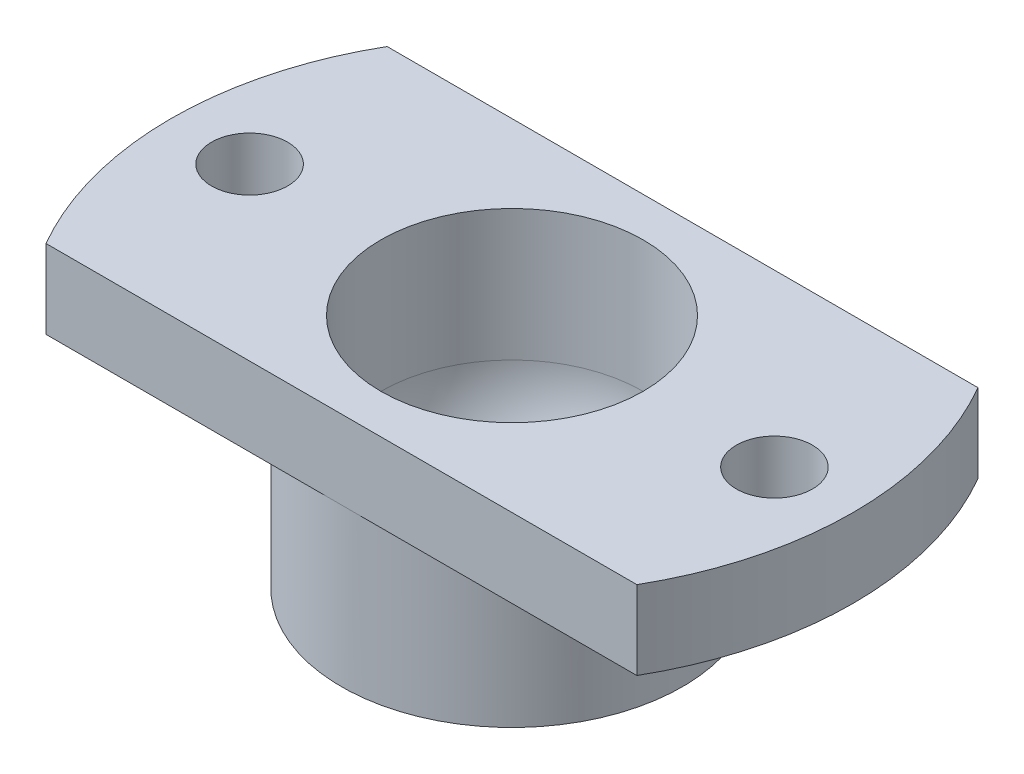
SolidWorks part; units mm, degrees
material "ABS"
ref_plane "Front Plane" through (0, 0, 0) normal (0, 0, 1) x (1, 0, 0)
ref_plane "Top Plane" through (0, 0, 0) normal (0, 1, 0) x (1, 0, 0)
ref_plane "Right Plane" through (0, 0, 0) normal (1, 0, 0) x (0, 0, -1)
sketch "Sketch1" plane through (0, 0, 0) normal (1, 0, 0) x (0, 0, -1)
  line L0 (-13, 5) -> (-5, 5)
  line L1 (-13, 5) -> (-13, 2)
  line L2 (0, 0) -> (0, 10.3505) construction
  line L3 (-13, 2) -> (-6.5, 2)
  line L4 (-5, 0) -> (-5, 5)
  line L6 (-6.5, -4) -> (-3, -4)
  line L7 (-6.5, -4) -> (-6.5, 2)
  arc A0 (-5, 0) -> (-3, -4) centre (0, 0) ccw
  dimension "D1" = 13
  dimension "D2" = 5
  dimension "D4" = 3
  dimension "D5" = 6.5
  dimension "D6" = 4
revolve "Revolve1" add sketch "Sketch1" angle 360 about L2
hole_wizard "M2.5 Clearance Hole1" positions "Sketch4" profile "Sketch3" hole size "M2.5" standard "ISO"
sketch "Sketch4" plane through (0, 2, 0) normal (0, -1, 0) x (-1, 0, 0)
  point P0 (10, 0)
  dimension "D1" = 10
sketch "Sketch3" plane through (-10, 2, 0) normal (1, 0, 0) x (0, 0, -1)
  line L0 (0, 0) -> (0, 10.8712)
  line L1 (0, 10.8712) -> (1.45, 10)
  line L2 (1.45, 10) -> (1.45, 0)
  line L5 (1.45, 0) -> (0, 0)
  line L10 (0, 10.8712) -> (-1.45, 10) construction
  line L11 (0, -6.35) -> (0, 107.95) construction
  dimension "Hole Dia." = 2.9
  dimension "Hole Depth" = 10
  dimension "Drill Angle" = 118
pattern_circular "CirPattern2" count 2 over 360 of "M2.5 Clearance Hole1"
sketch "Sketch5" plane through (0, 2, 0) normal (0, -1, 0) x (1, 0, 0)
  line L1 (-17.0763, 6.5) -> (20.9148, 6.5)
  line L2 (-17.0763, 6.5) -> (-17.0763, -6.5)
  line L3 (-17.0763, -6.5) -> (20.9148, -6.5)
  line L4 (20.9148, 6.5) -> (20.9148, -6.5)
  line L5 (-23.7253, 17.7727) -> (26.7016, 17.7727)
  line L6 (-23.7253, 17.7727) -> (-23.7253, -15.7319)
  line L7 (-23.7253, -15.7319) -> (26.7016, -15.7319)
  line L8 (26.7016, 17.7727) -> (26.7016, -15.7319)
  circle A0 centre (0, 0) radius 6.5 construction
  circle A1 centre (0, 0) radius 6.5 construction
extrude "Cut-Extrude1" cut sketch "Sketch5" against normal through all
